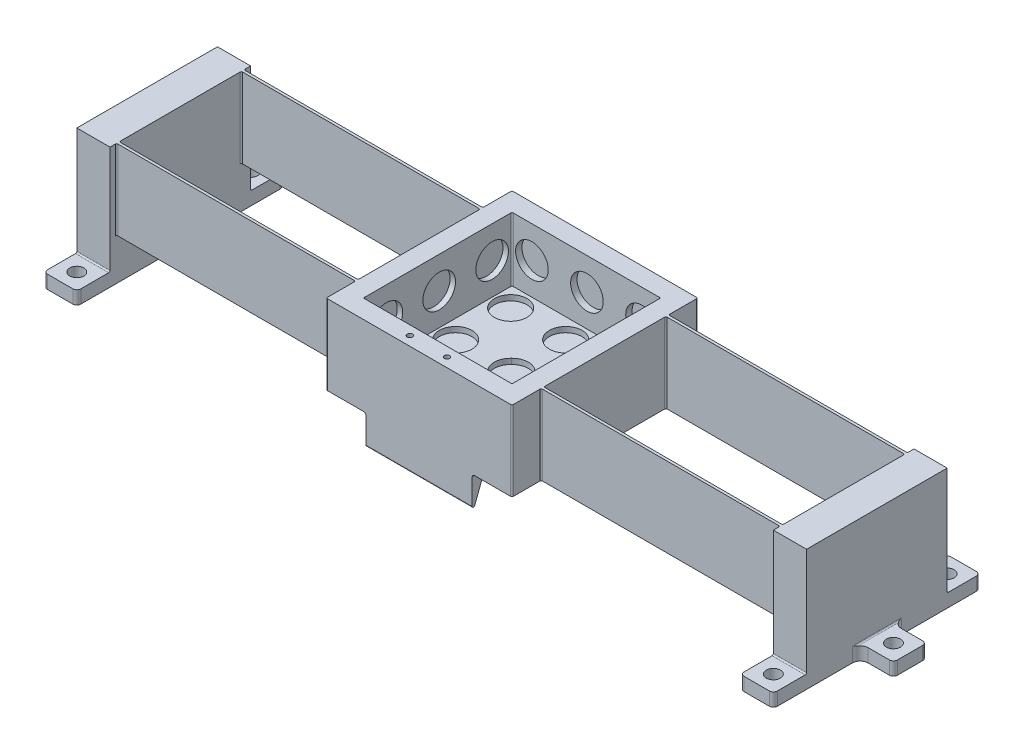
SolidWorks part; units mm, degrees
ref_plane "Front Plane" through (0, 0, 0) normal (0, 0, 1) x (1, 0, 0)
ref_plane "Top Plane" through (0, 0, 0) normal (0, 1, 0) x (1, 0, 0)
ref_plane "Right Plane" through (0, 0, 0) normal (1, 0, 0) x (0, 0, -1)
sketch "Sketch1" plane through (0, 0, 0) normal (0, 1, 0) x (1, 0, 0)
  line L1 (-35, -35) -> (35, -35)
  line L2 (-35, -35) -> (-35, 35)
  line L3 (-35, 35) -> (35, 35)
  line L4 (35, -35) -> (35, 35)
  line L5 (-35, -35) -> (35, 35) construction
  line L6 (-35, 35) -> (35, -35) construction
  point P0 (0, 0)
  dimension "D1" = 70
  dimension "D2" = 70
extrude "Boss-Extrude1" add sketch "Sketch1" along normal blind 30
shell "Shell1" thickness 7 removed face at (0, 30, 0)
sketch "Sketch2" plane through (0, 30, 0) normal (0, 1, 0) x (1, 0, 0)
  line L0 (-35, 35) -> (-35, -35) construction
  line L1 (-28, -28) -> (28, -28) construction
  line L2 (-28, -28) -> (-28, 28) construction
  line L3 (-28, 28) -> (28, 28) construction
  line L4 (28, -28) -> (28, 28) construction
  line L5 (-28, -28) -> (28, 28) construction
  line L6 (-28, 28) -> (28, -28) construction
  line L7 (35, 35) -> (-35, 35) construction
  point P0 (0, 0)
  dimension "D1" = 7
  dimension "D2" = 7
sketch "Sketch3" plane through (35, 0, 0) normal (1, 0, 0) x (0, 0, -1)
  line L0 (-35, 30) -> (35, 30) construction
  line L1 (-24, 30) -> (-23, 30)
  line L2 (-24, 30) -> (-24, 0)
  line L3 (-24, 0) -> (-23, 0)
  line L4 (-23, 30) -> (-23, 0)
  line L5 (-35, 0) -> (35, 0) construction
  line L11 (28, 30) -> (-28, 30) construction
  line L12 (24, 30) -> (23, 30)
  line L13 (24, 30) -> (24, 0)
  line L14 (24, 0) -> (23, 0)
  line L15 (23, 30) -> (23, 0)
  line L16 (-23.5, 30) -> (-23.5, 0) construction
  line L18 (23.5, 0) -> (23.5, 30) construction
  point P8 (0, 0)
  dimension "D1" = 1
  dimension "D2" = 23
  dimension "D3" = 23
extrude "Boss-Extrude2" add sketch "Sketch3" along normal blind 90
sketch "Sketch5" plane through (125, 0, 0) normal (1, 0, 0) x (0, 0, -1)
  line L0 (-24, 30) -> (-24, 0) construction
  line L1 (-26.5, 30) -> (26.5, 30)
  line L2 (-26.5, 30) -> (-26.5, 0)
  line L3 (-26.5, 0) -> (26.5, 0)
  line L4 (26.5, 30) -> (26.5, 0)
  line L5 (28, 30) -> (-28, 30) construction
  line L6 (24, 0) -> (35, 0) construction
  line L7 (24, 0) -> (24, 30) construction
  dimension "D1" = 2.5
  dimension "D2" = 2.5
extrude "Boss-Extrude3" add sketch "Sketch5" along normal blind 12.5
sketch "Sketch6" plane through (0, 0, 0) normal (0, -1, 0) x (1, 0, 0)
  line L1 (125, 26.5) -> (137.5, 26.5)
  line L2 (125, 26.5) -> (125, -26.5)
  line L3 (125, -26.5) -> (137.5, -26.5)
  line L4 (137.5, 26.5) -> (137.5, -26.5)
extrude "Boss-Extrude4" add sketch "Sketch6" along normal blind 15.75
sketch "Sketch8" plane through (0, -15.75, 0) normal (0, -1, 0) x (1, 0, 0)
  line L1 (137.5, -26.5) -> (125, -26.5)
  line L2 (137.5, -26.5) -> (137.5, -39)
  line L3 (137.5, -39) -> (125, -39)
  line L4 (125, -26.5) -> (125, -39)
  line L5 (137.5, 26.5) -> (125, 26.5)
  line L6 (137.5, 26.5) -> (137.5, 39)
  line L7 (137.5, 39) -> (125, 39)
  line L8 (125, 26.5) -> (125, 39)
  line L13 (137.5, -26.5) -> (137.5, 26.5) construction
  line L14 (150, -6.25) -> (137.5, -6.25)
  line L15 (150, -6.25) -> (150, 6.25)
  line L16 (150, 6.25) -> (137.5, 6.25)
  line L17 (137.5, -6.25) -> (137.5, 6.25)
  line L18 (150, -6.25) -> (137.5, 6.25) construction
  line L19 (150, 6.25) -> (137.5, -6.25) construction
  line L20 (137.5, 0) -> (150, 0) construction
  point P13 (143.75, 0)
  point P19 (137.5, 0)
  point P20 (137.5, 0)
extrude "Boss-Extrude5" add sketch "Sketch8" against normal blind 5
hole_wizard "Ø5.0mm Dowel Hole1" positions "Sketch9" profile "Sketch10" hole size "Ø5.0" standard "ANSI Metric"
sketch "Sketch9" plane through (0, -10.75, 0) normal (0, 1, 0) x (1, 0, 0)
  line L0 (131.25, 39) -> (131.25, 32.75) construction
  line L1 (125, 39) -> (137.5, 39) construction
  line L2 (131.25, 32.75) -> (137.5, 32.75) construction
  line L3 (137.5, 39) -> (137.5, 26.5) construction
  line L5 (137.5, 0) -> (143.75, 0) construction
  line L6 (137.5, -6.25) -> (137.5, 6.25) construction
  line L7 (143.75, 0) -> (143.75, 6.25) construction
  line L8 (137.5, 6.25) -> (150, 6.25) construction
  line L10 (131.25, -26.5) -> (131.25, -32.75) construction
  line L11 (125, -26.5) -> (137.5, -26.5) construction
  line L12 (131.25, -32.75) -> (137.5, -32.75) construction
  line L13 (137.5, -26.5) -> (137.5, -39) construction
  point P0 (131.25, 32.75)
  point P2 (143.75, 0)
  point P4 (131.25, -32.75)
sketch "Sketch10" plane through (131.25, -10.75, -32.75) normal (1, 0, 0) x (0, 0, 1)
  line L0 (0, 0) -> (0, 18.1023)
  line L1 (0, 18.1023) -> (2.65, 16.51)
  line L2 (2.65, 16.51) -> (2.65, 0)
  line L5 (2.65, 0) -> (0, 0)
  line L10 (0, 18.1023) -> (-2.65, 16.51) construction
  line L11 (0, -6.35) -> (0, 107.95) construction
  dimension "Hole Dia." = 5.3
  dimension "Hole Depth" = 16.51
  dimension "Drill Angle" = 118
mirror "Mirror1" about plane through (0, 0, 0) normal (1, 0, 0) of "Boss-Extrude2", "Boss-Extrude3", "Boss-Extrude5", "Boss-Extrude4", "Ø5.0mm Dowel Hole1"
fillet "Fillet1" radius 0.5 20 edges at (131.25, -10.75, 26.5) (-125, 15, 24) (-125, 15, 23) (-35, 15, 24) (-35, 15, 23) (-125, 15, -24) (-125, 15, -23) (-35, 15, -24) (-35, 15, -23) (-131.25, -10.75, -26.5) (-131.25, -10.75, 26.5) (35, 15, 24) (35, 15, 23) (125, 15, 24) (125, 15, 23) (35, 15, -24) (35, 15, -23) (125, 15, -24) (125, 15, -23) (131.25, -10.75, -26.5)
fillet "Fillet2" radius 1.5 12 edges at (150, -13.25, 6.25) (150, -13.25, -6.25) (137.5, -13.25, -39) (125, -13.25, -39) (137.5, -13.25, 39) (125, -13.25, 39) (-125, -13.25, -39) (-137.5, -13.25, -39) (-150, -13.25, -6.25) (-150, -13.25, 6.25) (-125, -13.25, 39) (-137.5, -13.25, 39)
sketch "Sketch11" plane through (0, 6, 0) normal (0, 1, 0) x (1, 0, 0)
  line L26 (-28, -28) -> (-28, 28) construction
  line L32 (-28, -28) -> (28, -28) construction
  circle A0 centre (-21, -21) radius 6.15
  dimension "D1" = 12.3
  dimension "D2" = 0.85
  dimension "D3" = 0.85
extrude "Cut-Extrude1" cut sketch "Sketch11" against normal blind 2.05
pattern_linear "LPattern1" count 3 spacing 20.75 along (1, 0, 0) count 3 spacing 20.75 along (0, 0, -1) of "Cut-Extrude1"
sketch "Sketch14" plane through (0, 6, 0) normal (0, 1, 0) x (1, 0, 0)
  line L0 (-28, 0) -> (0, 0) construction
  line L1 (-28, 28) -> (-28, -28) construction
  line L2 (0, 0) -> (0, -28) construction
  line L3 (-28, -28) -> (28, -28) construction
  circle A0 centre (0, 0) radius 6.15
  dimension "D1" = 12.3
extrude "Cut-Extrude4" cut sketch "Sketch14" against normal blind 2.05
sketch "Sketch12" plane through (-28, 0, 0) normal (1, 0, 0) x (0, 0, -1)
  line L5 (-28, 18) -> (-19.35, 18) construction
  line L6 (-28, 30) -> (-28, 6) construction
  circle A0 centre (-19.35, 18) radius 6.15
  dimension "D1" = 12.3
  dimension "D2" = 2.5
extrude "Cut-Extrude2" cut sketch "Sketch12" against normal blind 2.05
pattern_linear "LPattern2" count 3 spacing 19.925 along (0, 0, -1) of "Cut-Extrude2"
sketch "Sketch13" plane through (0, 0, -28) normal (0, 0, -1) x (-1, 0, 0)
  line L6 (-28, 30) -> (-28, 6) construction
  line L7 (-21, 18) -> (-28, 18) construction
  circle A0 centre (-21, 18) radius 6.15
  dimension "D1" = 12.3
  dimension "D3" = 0.85
extrude "Cut-Extrude3" cut sketch "Sketch13" along normal blind 2.4
pattern_linear "LPattern3" count 3 spacing 20.75 along (-1, 0, 0) of "Cut-Extrude3"
mirror "Mirror2" about plane through (0, 0, 0) normal (1, 0, 0) of "LPattern2", "Cut-Extrude2"
fillet "Fillet3" radius 0.5 4 edges at (28, 18, -28) (-28, 18, -28) (28, 18, 28) (-28, 18, 28)
fillet "Fillet4" radius 0.5 4 edges at (-35, 15, 35) (35, 15, 35) (-35, 15, -35) (35, 15, -35)
sketch "Sketch19" plane through (0, 0, 0) normal (1, 0, 0) x (0, 0, -1)
  line L0 (-30, 0) -> (-35, -13.25)
  line L1 (-35, -13.25) -> (-35, 0)
  line L2 (-35, 0) -> (-30, 0)
  line L3 (0, 0) -> (-30, 0) construction
  line L4 (37.5, -15.75) -> (-37.5, -15.75) construction
  dimension "D1" = 5
  dimension "D2" = 30
  dimension "D3" = 2.5
extrude "Boss-Extrude8" add sketch "Sketch19" along normal mid plane 40
sketch "Sketch20" plane through (0, 0, 0) normal (1, 0, 0) x (0, 0, -1)
  line L0 (-35, 20) -> (-42.5, 20)
  line L1 (-42.5, 20) -> (-42.5, 30)
  line L2 (-26.5, 30) -> (-42.5, 30) construction
  line L5 (-42.5, 30) -> (-40, 30)
  line L6 (-40, 30) -> (-40, 22.5)
  line L7 (-40, 22.5) -> (-35, 22.5)
  line L8 (-35, 22.5) -> (-35, 20)
  line L9 (-35, 30) -> (-35, 0) construction
  line L10 (-35, 0) -> (-35, 30) construction
  dimension "D1" = 5
  dimension "D2" = 10
  dimension "D3" = 2.5
  dimension "D4" = 2.5
extrude "Place For Sensor" [suppressed] add sketch "Sketch20" along normal mid plane 10
fillet "Place For Sensor Fillet5" [suppressed] radius 0.5
fillet "Place For Sensor Fillet6" [suppressed] radius 1.5
hole_wizard "Place For Sensor Ø3.0mm Dowel Hole2" [suppressed] positions "Sketch21" profile "Sketch22" hole size "Ø3.0" standard "ANSI Metric"
sketch "Sketch21" [suppressed] plane through (0, 0, 32.5) normal (0, 0, 1) x (1, 0, 0)
  line L0 (-2.5, 27.5) -> (2.5, 27.5) construction
  line L2 (-18, 30) -> (18, 30) construction
  line L3 (-5, 28.5) -> (-5, 20.5) construction
  line L4 (5, 28.5) -> (5, 20.5) construction
  point P0 (-2.5, 27.5)
  point P2 (2.5, 27.5)
  dimension "D1" = 2.5
  dimension "D2" = 2.5
  dimension "D3" = 2.5
sketch "Sketch22" plane through (-2.5, 27.5, 32.5) normal (1, 0, 0) x (0, -1, 0)
  line L0 (0, 0) -> (0, 2.5)
  line L1 (0, 2.5) -> (1.65, 2.5)
  line L2 (1.65, 2.5) -> (1.65, 0)
  line L5 (1.65, 0) -> (0, 0)
  line L11 (0, -6.35) -> (0, 107.95) construction
  dimension "Thru Hole Dia." = 3.3
  dimension "Thru Hole Depth" = 2.5
sketch "Sketch23" plane through (0, 30, 0) normal (0, 1, 0) x (1, 0, 0)
  line L1 (-28, -28) -> (28, -28) construction
  circle A0 centre (-7, -31.5) radius 1
  circle A1 centre (7, -31.5) radius 1
  dimension "D4" = 2
  dimension "D1" = 3.5
  dimension "D2" = 14
  dimension "D3" = 7
extrude "Cut-Extrude5" cut sketch "Sketch23" against normal blind 6
fillet "Fillet5" radius 0.5 1 edges at (0, -13.25, 35)
fillet "Fillet6" radius 1 3 edges at (-20, 0, 32.5) (20, 0, 32.5) (0, 0, 30)
fillet "Fillet8" radius 3 4 edges at (137.5, -13, 6.25) (137.5, -13, -6.25) (-137.5, -13, -6.25) (-137.5, -13, 6.25)
